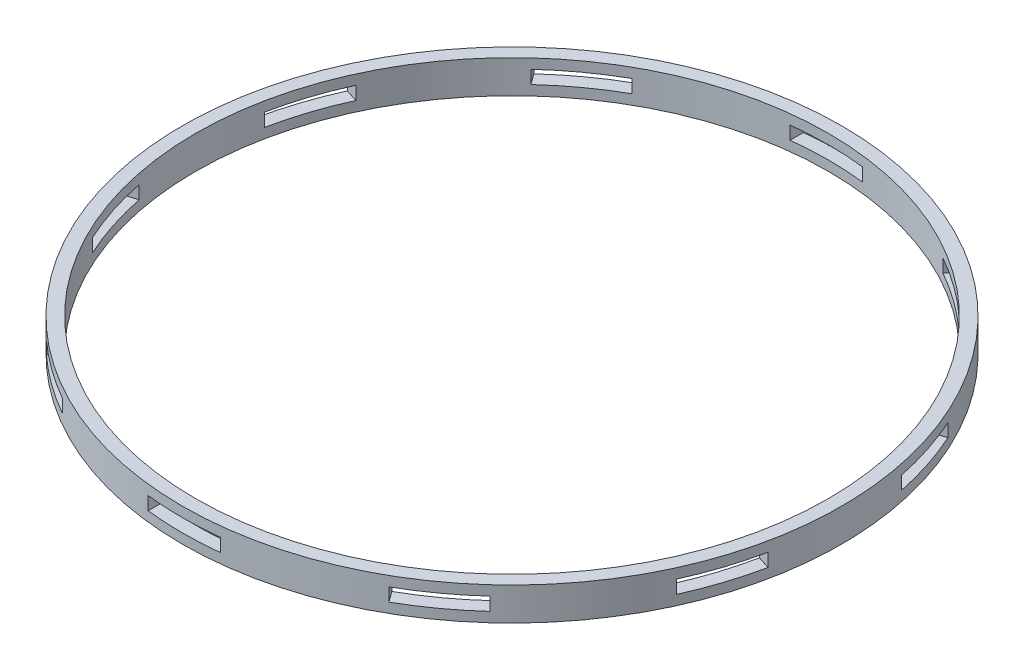
SolidWorks part; units mm, degrees
ref_plane "Front Plane" through (0, 0, 0) normal (0, 0, 1) x (1, 0, 0)
ref_plane "Top Plane" through (0, 0, 0) normal (0, 1, 0) x (1, 0, 0)
ref_plane "Right Plane" through (0, 0, 0) normal (1, 0, 0) x (0, 0, -1)
sketch "Sketch1" plane through (0, 0, 0) normal (0, 1, 0) x (1, 0, 0)
  line L0 (40.8443, 86.8778) -> (42.5461, 90.4977) construction
  circle A0 centre (0, 0) radius 96
  circle A1 centre (0, 0) radius 100
  dimension "D2" = 192
  dimension "D1" = 4
extrude "Boss-Extrude1" add sketch "Sketch1" along normal blind 10
sketch "Sketch2" plane through (0, 0, 0) normal (0, 0, 1) x (1, 0, 0)
  line L0 (-100, 0) -> (100, 0) construction
  line L1 (-11, 7) -> (11, 7)
  line L2 (-11, 7) -> (-11, 3)
  line L3 (-11, 3) -> (11, 3)
  line L4 (11, 7) -> (11, 3)
  line L5 (96, 10) -> (-96, 10) construction
  point P11 (0, 3)
  dimension "D1" = 3
  dimension "D2" = 3
  dimension "D3" = 22
extrude "Cut-Extrude1" cut sketch "Sketch2" against normal through all
ref_axis "Axis1" through (0, 10, 0) along (0, -1, 0)
pattern_circular "CirPattern1" count 10 over 360 about axis through (0, 10, 0) along (0, -1, 0) of "Cut-Extrude1"
